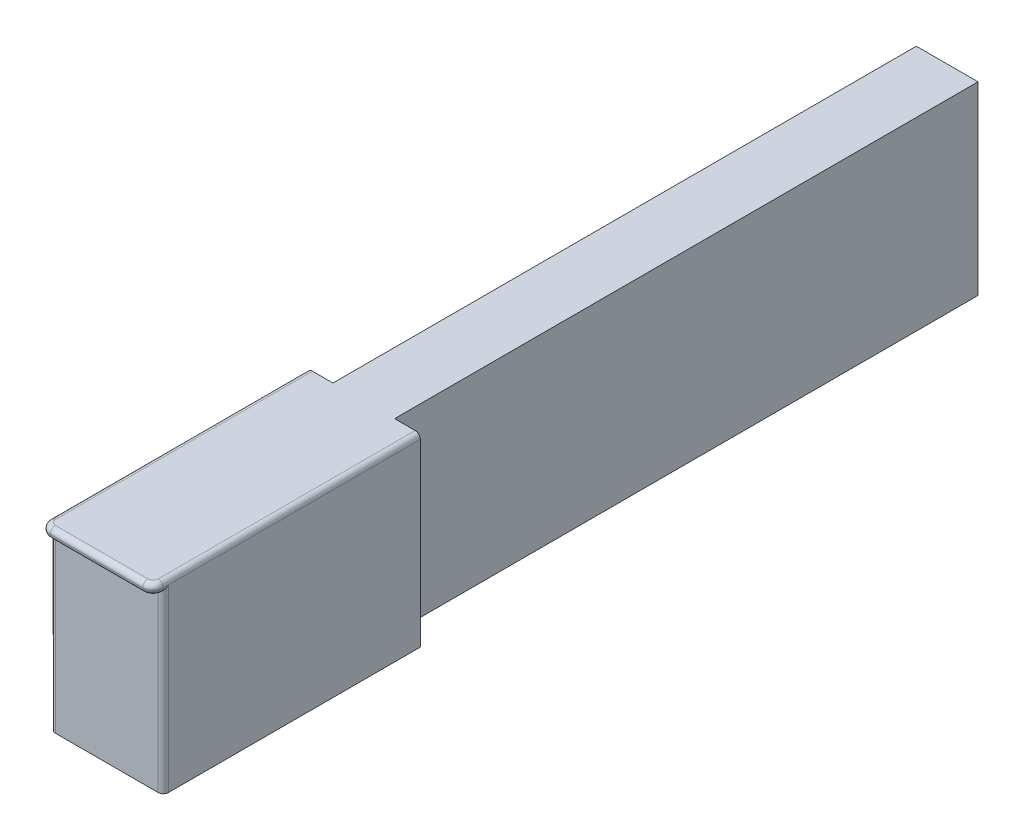
SolidWorks part; units mm, degrees
ref_plane "Front Plane" through (0, 0, 0) normal (0, 0, 1) x (1, 0, 0)
ref_plane "Top Plane" through (0, 0, 0) normal (0, 1, 0) x (1, 0, 0)
ref_plane "Right Plane" through (0, 0, 0) normal (1, 0, 0) x (0, 0, -1)
sketch "Sketch1" plane through (0, 0, 0) normal (0, 1, 0) x (1, 0, 0)
  line L1 (-11, -81.75) -> (11, -81.75)
  line L2 (-11, -81.75) -> (-11, 81.75)
  line L3 (-11, 81.75) -> (11, 81.75)
  line L4 (11, -81.75) -> (11, 81.75)
  line L5 (-11, -81.75) -> (11, 81.75) construction
  line L6 (-11, 81.75) -> (11, -81.75) construction
  point P0 (0, 0)
  dimension "D1" = 163.5
  dimension "D2" = 22
extrude "Boss-Extrude1" add sketch "Sketch1" along normal blind 36 contours L2 L3 L4 L1
fillet "Fillet1" radius 1 2 edges at (-11, 18, 81.75) (11, 18, 81.75)
sketch "Sketch2" plane through (0, 36, 0) normal (0, 1, 0) x (1, 0, 0)
  line L0 (11, -80.75) -> (11, 81.75) construction
  line L1 (-11, 81.75) -> (11, 81.75)
  line L2 (-11, 81.75) -> (-11, -83.75)
  line L3 (-11, -83.75) -> (11, -83.75)
  line L4 (11, 81.75) -> (11, -83.75)
  line L5 (-10, -81.75) -> (10, -81.75) construction
  dimension "D1" = 2
extrude "Boss-Extrude2" add sketch "Sketch2" against normal blind 2
fillet "Fillet2" radius 2 2 edges at (-11, 35, 83.75) (11, 35, 83.75)
fillet "Fillet3" radius 1 10 edges at (-11, 34, 81.25) (-10.4142, 34, 83.1642) (11, 34, 81.25) (10.4142, 34, 83.1642) (11, 36, 0) (10.4142, 36, 83.1642) (0, 36, 83.75) (-10.4142, 36, 83.1642) (-11, 36, 0) (0, 34, 83.75)
sketch "Sketch3" plane through (0, 36, 0) normal (0, 1, 0) x (1, 0, 0)
  line L1 (7.5, -31.75) -> (11, -31.75)
  line L2 (7.5, -31.75) -> (7.5, 81.75)
  line L3 (7.5, 81.75) -> (11, 81.75)
  line L4 (11, -31.75) -> (11, 81.75)
  line L5 (7.5, -31.75) -> (11, 81.75) construction
  line L6 (7.5, 81.75) -> (11, -31.75) construction
  line L7 (-10, -81.75) -> (10, -81.75) construction
  line L8 (-11, 81.75) -> (11, 81.75) construction
  line L9 (11, 81.75) -> (11, -80.75) construction
  dimension "D1" = 3.5
  dimension "D2" = 50
extrude "Cut-Extrude2" [suppressed] cut sketch "Sketch3" against normal through all
sketch "Sketch5" plane through (-11, 0, 0) normal (-1, 0, 0) x (0, 0, 1)
  line L0 (81.75, 34) -> (81.75, 0) construction
  line L1 (80.75, 0) -> (-81.75, 0) construction
  line L2 (-81.75, 36) -> (81.75, 36) construction
  line L3 (-81.75, 35) -> (-81.75, 0) construction
  line L8 (31.75, 36) -> (-81.75, 36)
  line L9 (31.75, 0) -> (31.75, 36)
  line L10 (-81.75, 0) -> (31.75, 0)
  line L11 (-81.75, 36) -> (-81.75, 0)
  dimension "D1" = 50
extrude "Cut-Extrude4" [suppressed] cut sketch "Sketch5" against normal blind 3.5
sketch "Sketch4" [suppressed] plane through (7.5, 0, 0) normal (1, 0, 0) x (0, 0, -1)
  line L4 (81.75, 36) -> (-31.75, 36)
  line L5 (-31.75, 36) -> (-31.75, 0)
  line L6 (-31.75, 0) -> (81.75, 0)
  line L7 (81.75, 0) -> (81.75, 36)
  line L8 (81.75, 36) -> (-31.75, 36)
  line L9 (-31.75, 36) -> (-31.75, 0)
  line L10 (-31.75, 0) -> (81.75, 0)
  line L11 (81.75, 0) -> (81.75, 36)
  dimension "D1" = 0
extrude "Cut-Extrude3" [suppressed] cut sketch "Sketch4" against normal blind 3.25
sketch "Sketch6" [suppressed] plane through (-7.5, 0, 0) normal (-1, 0, 0) x (0, 0, 1)
  line L4 (-81.75, 36) -> (-81.75, 0)
  line L5 (-81.75, 0) -> (31.75, 0)
  line L6 (31.75, 0) -> (31.75, 36)
  line L7 (31.75, 36) -> (-81.75, 36)
  line L8 (-81.75, 36) -> (-81.75, 0)
  line L9 (-81.75, 0) -> (31.75, 0)
  line L10 (31.75, 0) -> (31.75, 36)
  line L11 (31.75, 36) -> (-81.75, 36)
  dimension "D1" = 0
extrude "Cut-Extrude5" [suppressed] cut sketch "Sketch6" against normal blind 3.25
sketch "White" plane through (0, 0, 0) normal (0, 1, 0) x (1, 0, 0)
  line L0 (12.5, -81.75) -> (34.5, -81.75)
  line L1 (-11, -81.75) -> (11, -81.75)
  line L2 (-11, -81.75) -> (-11, 81.75)
  line L3 (-11, 81.75) -> (11, 81.75)
  line L4 (11, -81.75) -> (11, 81.75)
  line L5 (12.5, -81.75) -> (12.5, 81.75)
  line L6 (12.5, 81.75) -> (34.5, 81.75)
  line L7 (34.5, -81.75) -> (34.5, 81.75)
  line L8 (36, -81.75) -> (58, -81.75)
  line L9 (36, -81.75) -> (36, 81.75)
  line L10 (36, 81.75) -> (58, 81.75)
  line L11 (58, -81.75) -> (58, 81.75)
  line L12 (59.5, -81.75) -> (81.5, -81.75)
  line L13 (59.5, -81.75) -> (59.5, 81.75)
  line L14 (59.5, 81.75) -> (81.5, 81.75)
  line L15 (81.5, -81.75) -> (81.5, 81.75)
  line L16 (83, -81.75) -> (105, -81.75)
  line L17 (83, -81.75) -> (83, 81.75)
  line L18 (83, 81.75) -> (105, 81.75)
  line L19 (105, -81.75) -> (105, 81.75)
  line L20 (106.5, -81.75) -> (128.5, -81.75)
  line L21 (106.5, -81.75) -> (106.5, 81.75)
  line L22 (106.5, 81.75) -> (128.5, 81.75)
  line L23 (128.5, -81.75) -> (128.5, 81.75)
  line L24 (130, -81.75) -> (152, -81.75)
  line L25 (130, -81.75) -> (130, 81.75)
  line L26 (130, 81.75) -> (152, 81.75)
  line L27 (152, -81.75) -> (152, 81.75)
  dimension "D1" = 7
sketch "Black" plane through (0, 0, 0) normal (0, 1, 0) x (1, 0, 0)
  line L0 (-11, 81.75) -> (11, 81.75) construction
  line L1 (16, -31.75) -> (4, -31.75)
  line L2 (16, -31.75) -> (16, 81.75)
  line L3 (16, 81.75) -> (4, 81.75)
  line L4 (4, -31.75) -> (4, 81.75)
  line L6 (31, -31.75) -> (43, -31.75)
  line L7 (31, -31.75) -> (31, 81.75)
  line L8 (31, 81.75) -> (43, 81.75)
  line L9 (43, -31.75) -> (43, 81.75)
  line L10 (12.5, -81.75) -> (34.5, -81.75) construction
  line L11 (16, -31.75) -> (31, -31.75) construction
  line L12 (36, 81.75) -> (58, 81.75) construction
  line L13 (106.5, 81.75) -> (128.5, 81.75) construction
  line L14 (111.75, 81.75) -> (99.75, 81.75)
  line L15 (111.75, 81.75) -> (111.75, -31.75)
  line L16 (111.75, -31.75) -> (99.75, -31.75)
  line L17 (99.75, 81.75) -> (99.75, -31.75)
  line L18 (83, 81.75) -> (105, 81.75) construction
  line L19 (126.75, 81.75) -> (138.75, 81.75)
  line L20 (126.75, 81.75) -> (126.75, -31.75)
  line L21 (126.75, -31.75) -> (138.75, -31.75)
  line L22 (138.75, 81.75) -> (138.75, -31.75)
  line L23 (84.75, 81.75) -> (72.75, 81.75)
  line L24 (84.75, 81.75) -> (84.75, -31.75)
  line L25 (84.75, -31.75) -> (72.75, -31.75)
  line L26 (72.75, 81.75) -> (72.75, -31.75)
  line L27 (105, -81.75) -> (106.5, -81.75) construction
  point P14 (23.5, -81.75)
  point P15 (23.5, -31.75)
  point P36 (105.75, -81.75)
  point P37 (105.75, -31.75)
  dimension "D1" = 50
  dimension "D2" = 12
  dimension "D3" = 12
  dimension "D4" = 15
  dimension "D5" = 15
  dimension "D6" = 15
sketch "Sketch11" plane through (0, 36, 0) normal (0, 1, 0) x (1, 0, 0)
  line L1 (11, 81.75) -> (2.5, 81.75)
  line L2 (11, 81.75) -> (11, -31.75)
  line L3 (11, -31.75) -> (2.5, -31.75)
  line L4 (2.5, 81.75) -> (2.5, -31.75)
  line L5 (16, -31.75) -> (4, -31.75) construction
  dimension "D1" = 8.5
extrude "C" [suppressed] cut sketch "Sketch11" against normal through all
sketch "Sketch12" plane through (0, 36, 0) normal (0, 1, 0) x (1, 0, 0)
  line L0 (31, -31.75) -> (43, -31.75) construction
  line L1 (-11, 81.75) -> (-6, 81.75)
  line L2 (-11, 81.75) -> (-11, -31.75)
  line L3 (-11, -31.75) -> (-6, -31.75)
  line L4 (-6, 81.75) -> (-6, -31.75)
  line L5 (11, 81.75) -> (6, 81.75)
  line L6 (11, 81.75) -> (11, -31.75)
  line L7 (11, -31.75) -> (6, -31.75)
  line L8 (6, 81.75) -> (6, -31.75)
  dimension "D1" = 5
  dimension "D2" = 5
extrude "D" cut sketch "Sketch12" against normal through all
sketch "Sketch13" plane through (0, 36, 0) normal (0, 1, 0) x (1, 0, 0)
  line L1 (-11, 81.75) -> (-2.5, 81.75)
  line L2 (-11, 81.75) -> (-11, -31.75)
  line L3 (-11, -31.75) -> (-2.5, -31.75)
  line L4 (-2.5, 81.75) -> (-2.5, -31.75)
  line L5 (16, -31.75) -> (4, -31.75) construction
  dimension "D1" = 8.5
extrude "E" [suppressed] cut sketch "Sketch13" against normal through all
sketch "Sketch14" plane through (0, 36, 0) normal (0, 1, 0) x (1, 0, 0)
  line L0 (16, -31.75) -> (4, -31.75) construction
  line L1 (11, 81.75) -> (0.75, 81.75)
  line L2 (11, 81.75) -> (11, -31.75)
  line L3 (11, -31.75) -> (0.75, -31.75)
  line L4 (0.75, 81.75) -> (0.75, -31.75)
  dimension "D1" = 10.25
extrude "F" [suppressed] cut sketch "Sketch14" against normal through all
sketch "Sketch15" plane through (0, 36, 0) normal (0, 1, 0) x (1, 0, 0)
  line L1 (-11, 81.75) -> (-7.75, 81.75)
  line L2 (-11, 81.75) -> (-11, -31.75)
  line L3 (-11, -31.75) -> (-7.75, -31.75)
  line L4 (-7.75, 81.75) -> (-7.75, -31.75)
  line L5 (11, 81.75) -> (4.25, 81.75)
  line L6 (11, 81.75) -> (11, -31.75)
  line L7 (11, -31.75) -> (4.25, -31.75)
  line L8 (4.25, 81.75) -> (4.25, -31.75)
  line L9 (16, -31.75) -> (4, -31.75) construction
  dimension "D1" = 3.25
  dimension "D2" = 6.75
extrude "G" [suppressed] cut sketch "Sketch15" against normal through all
sketch "Sketch16" plane through (0, 36, 0) normal (0, 1, 0) x (1, 0, 0)
  line L0 (16, -31.75) -> (4, -31.75) construction
  line L1 (-11, 81.75) -> (-4.25, 81.75)
  line L2 (-11, 81.75) -> (-11, -31.75)
  line L3 (-11, -31.75) -> (-4.25, -31.75)
  line L4 (-4.25, 81.75) -> (-4.25, -31.75)
  line L5 (11, 81.75) -> (7.75, 81.75)
  line L6 (11, 81.75) -> (11, -31.75)
  line L7 (11, -31.75) -> (7.75, -31.75)
  line L8 (7.75, 81.75) -> (7.75, -31.75)
  dimension "D1" = 6.75
  dimension "D2" = 3.25
extrude "A" [suppressed] cut sketch "Sketch16" against normal through all
sketch "Sketch17" plane through (0, 36, 0) normal (0, 1, 0) x (1, 0, 0)
  line L0 (16, -31.75) -> (4, -31.75) construction
  line L1 (-11, 81.75) -> (-0.75, 81.75)
  line L2 (-11, 81.75) -> (-11, -31.75)
  line L3 (-11, -31.75) -> (-0.75, -31.75)
  line L4 (-0.75, 81.75) -> (-0.75, -31.75)
  dimension "D1" = 10.25
extrude "B" [suppressed] cut sketch "Sketch17" against normal through all
